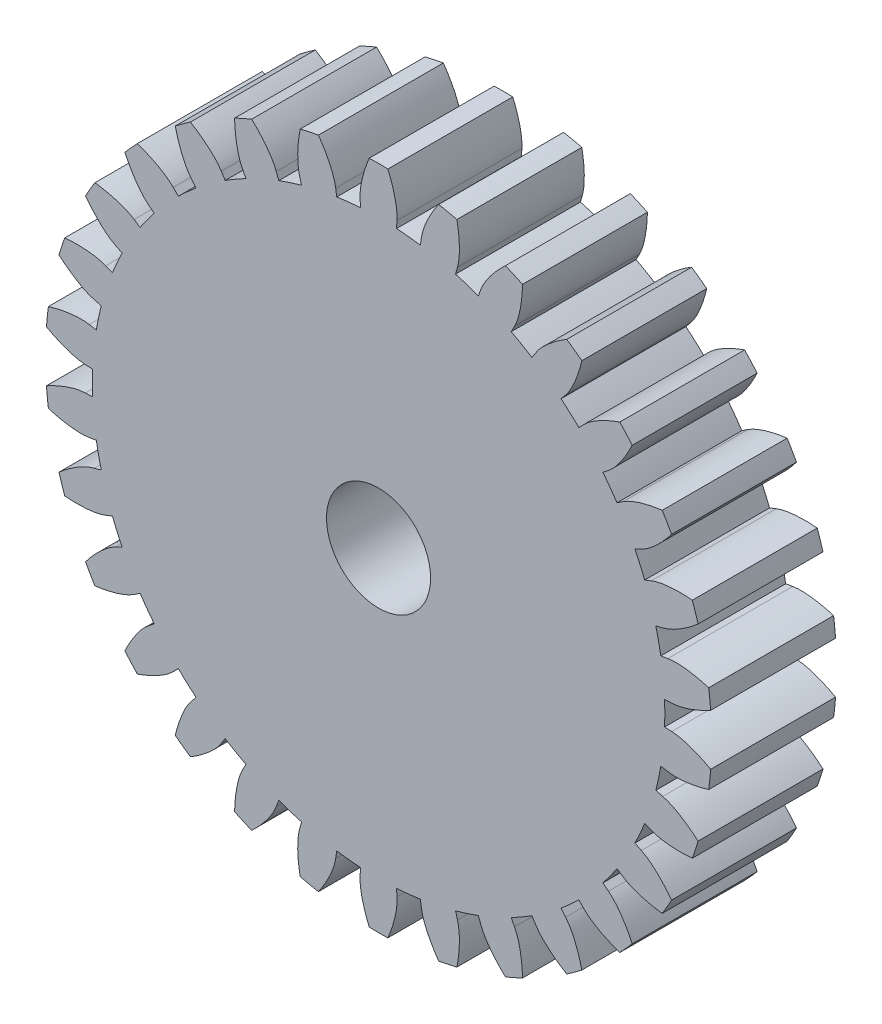
SolidWorks part; units mm, degrees
ref_plane "前视基准面" through (0, 0, 0) normal (0, 0, 1) x (1, 0, 0)
ref_plane "上视基准面" through (0, 0, 0) normal (0, 1, 0) x (1, 0, 0)
ref_plane "右视基准面" through (0, 0, 0) normal (1, 0, 0) x (0, 0, -1)
other "Configuration Table"
sketch "草图1" plane through (0, 0, 0) normal (0, 0, 1) x (1, 0, 0)
  line L0 (0, 0) -> (3, 0) construction
  line L1 (0, 0) -> (2.9959, 0.157) construction
  line L2 (0, 0) -> (2.8166, 0.1179)
  line L3 (2.9959, 0.157) -> (2.9959, -0.157) construction
  line L4 (0, 0) -> (2.8166, -0.1179)
  circle A0 centre (0, 0) radius 3.2
  circle A1 centre (0, 0) radius 3 construction
  circle A2 centre (0, 0) radius 2.75
  circle A3 centre (0, 0) radius 2.8191 construction
  circle A4 centre (0, 0) radius 0.5
  spline S0 degree 4 poles (2.8166, 0.1179) (2.8381, 0.1188) (2.8978, 0.1258) (3.0089, 0.1568) (3.1803, 0.2313) (3.3851, 0.3614) (3.6216, 0.564) (3.8603, 0.8405) (4.0761, 1.1785) (4.2561, 1.5715) (4.3861, 1.9834) (4.4688, 2.4072) (4.5085, 2.8585) (4.4993, 3.4194) (4.4024, 4.0825) (4.1788, 4.8285) (3.8049, 5.6087) (3.3237, 6.3268) (2.7489, 6.9731) (2.0986, 7.5407) (1.3811, 8.025) (0.6179, 8.4229) (-0.1939, 8.7334) (-0.914, 8.9278) (-1.5673, 9.0405) (-2.0388, 9.0934) (-2.4603, 9.1184) (-2.7399, 9.1248) (-3.1343, 9.1224) (-3.4319, 9.1032) (-3.7297, 9.081) (-3.8793, 9.0605) (-3.9757, 9.0498) knots 0 0 0 0 0 0.005604 0.015718 0.02996 0.048734 0.068727 0.096889 0.125051 0.153212 0.181374 0.209535 0.237696 0.271429 0.327752 0.384075 0.440398 0.496721 0.553044 0.609367 0.66569 0.722013 0.778336 0.834659 0.86282 0.890982 0.909091 0.931818 0.954545 0.977273 1 1 1 1 1 construction
  spline S1 degree 4 poles (2.8166, 0.1179) (2.8381, 0.1188) (2.8978, 0.1258) (3.0089, 0.1568) (3.1803, 0.2313) (3.3851, 0.3614) (3.6216, 0.564) (3.8603, 0.8405) (4.0761, 1.1785) (4.2561, 1.5715) (4.3861, 1.9834) (4.4688, 2.4072) (4.5085, 2.8585) (4.4993, 3.4194) (4.4024, 4.0825) (4.1788, 4.8285) (3.8049, 5.6087) (3.3237, 6.3268) (2.7489, 6.9731) (2.0986, 7.5407) (1.3811, 8.025) (0.6179, 8.4229) (-0.1939, 8.7334) (-0.914, 8.9278) (-1.5673, 9.0405) (-2.0388, 9.0934) (-2.3617, 9.1126) (-2.5224, 9.1187) (-2.5854, 9.1203) knots 0 0 0 0 0 0.005604 0.015718 0.02996 0.048734 0.068727 0.096889 0.125051 0.153212 0.181374 0.209535 0.237696 0.271429 0.327752 0.384075 0.440398 0.496721 0.553044 0.609367 0.66569 0.722013 0.778336 0.834659 0.86282 0.890982 0.909091 0.909091 0.909091 0.909091 0.909091
  spline S2 degree 4 poles (2.8166, -0.1179) (2.8381, -0.1188) (2.8978, -0.1258) (3.0089, -0.1568) (3.1803, -0.2313) (3.3851, -0.3614) (3.6216, -0.564) (3.8603, -0.8405) (4.0761, -1.1785) (4.2561, -1.5715) (4.3861, -1.9834) (4.4688, -2.4072) (4.5085, -2.8585) (4.4993, -3.4194) (4.4024, -4.0825) (4.1788, -4.8285) (3.8049, -5.6087) (3.3237, -6.3268) (2.7489, -6.9731) (2.0986, -7.5407) (1.3811, -8.025) (0.6179, -8.4229) (-0.1939, -8.7334) (-0.914, -8.9278) (-1.5673, -9.0405) (-2.0388, -9.0934) (-2.4603, -9.1184) (-2.7399, -9.1248) (-3.1343, -9.1224) (-3.4319, -9.1032) (-3.7297, -9.081) (-3.8793, -9.0605) (-3.9757, -9.0498) knots 0 0 0 0 0 0.005604 0.015718 0.02996 0.048734 0.068727 0.096889 0.125051 0.153212 0.181374 0.209535 0.237696 0.271429 0.327752 0.384075 0.440398 0.496721 0.553044 0.609367 0.66569 0.722013 0.778336 0.834659 0.86282 0.890982 0.909091 0.931818 0.954545 0.977273 1 1 1 1 1 construction
  spline S3 degree 4 poles (2.8166, -0.1179) (2.8381, -0.1188) (2.8978, -0.1258) (3.0089, -0.1568) (3.1803, -0.2313) (3.3851, -0.3614) (3.6216, -0.564) (3.8603, -0.8405) (4.0761, -1.1785) (4.2561, -1.5715) (4.3861, -1.9834) (4.4688, -2.4072) (4.5085, -2.8585) (4.4993, -3.4194) (4.4024, -4.0825) (4.1788, -4.8285) (3.8049, -5.6087) (3.3237, -6.3268) (2.7489, -6.9731) (2.0986, -7.5407) (1.3811, -8.025) (0.6179, -8.4229) (-0.1939, -8.7334) (-0.914, -8.9278) (-1.5673, -9.0405) (-2.0388, -9.0934) (-2.3617, -9.1126) (-2.5224, -9.1187) (-2.5854, -9.1203) knots 0 0 0 0 0 0.005604 0.015718 0.02996 0.048734 0.068727 0.096889 0.125051 0.153212 0.181374 0.209535 0.237696 0.271429 0.327752 0.384075 0.440398 0.496721 0.553044 0.609367 0.66569 0.722013 0.778336 0.834659 0.86282 0.890982 0.909091 0.909091 0.909091 0.909091 0.909091
  point P15 (2.9959, 0)
  dimension "齿顶圆直径" = 6.4
  dimension "分度圆直径" = 6
  dimension "齿根圆直径" = 5.5
  dimension "基圆直径" = 5.6382
  dimension "内孔直径" = 1
  dimension "渐近线镜像线夹角" = 3
extrude "凸台-拉伸1" add sketch "草图1" along normal blind 1.2 contours A0 | A4
extrude "切除-拉伸1" cut sketch "草图1<3>" along normal through all contours A2 S3 A0 S1 region at (3.0047, 0, 0)
sketch "草图1<3>" plane through (0, 0, 0) normal (0, 0, 1) x (1, 0, 0) same geometry as "草图1"
pattern_circular "阵列(圆周)1" count 30 every 12 about axis through (0, 0, 1.2) along (0, 0, 1) of "切除-拉伸1"
equation "\"m\"= 0.2'模数"
equation "\"z\"= 30'齿数"
equation "\"a\"= 20度'压力角"
equation "\"d\"= \"m\" * \"z\"'分度圆直径"
equation "\"da\"= ( \"z\" + 2 ) * \"m\"'齿顶圆直径"
equation "\"df\"= ( \"z\" - 2.5 ) * \"m\"'齿根圆直径"
equation "\"s\"= 0.5 * PI * \"m\"'分度圆齿厚"
equation "\"r\"= 0.38 * \"m\"'齿根圆角"
equation "\"B\"= 0.3 * \"d\"'齿厚"
equation "\"db\"= \"m\" * \"z\" * cos ( \"a\" )'基圆直径"
equation "\"rb\"= \"db\" / 2'基圆半径"
equation "\"齿顶圆直径@草图1\"= \"da\""
equation "\"分度圆直径@草图1\"= \"d\""
equation "\"齿根圆直径@草图1\"= \"df\""
equation "\"基圆直径@草图1\"= \"db\""
equation "\"渐近线镜像线夹角@草图1\"= 360 / 4 / \"z\""
equation "\"h\"= 1.2'齿轮厚度"
equation "\"ir\"= 1'内孔直径"
equation "\"内孔直径@草图1\"= \"ir\""
equation "\"齿轮厚@凸台-拉伸1\"= \"h\""
equation "\"齿轮夹角@阵列(圆周)1\"= 360 / \"z\""
equation "\"齿数@阵列(圆周)1\"= \"z\""
